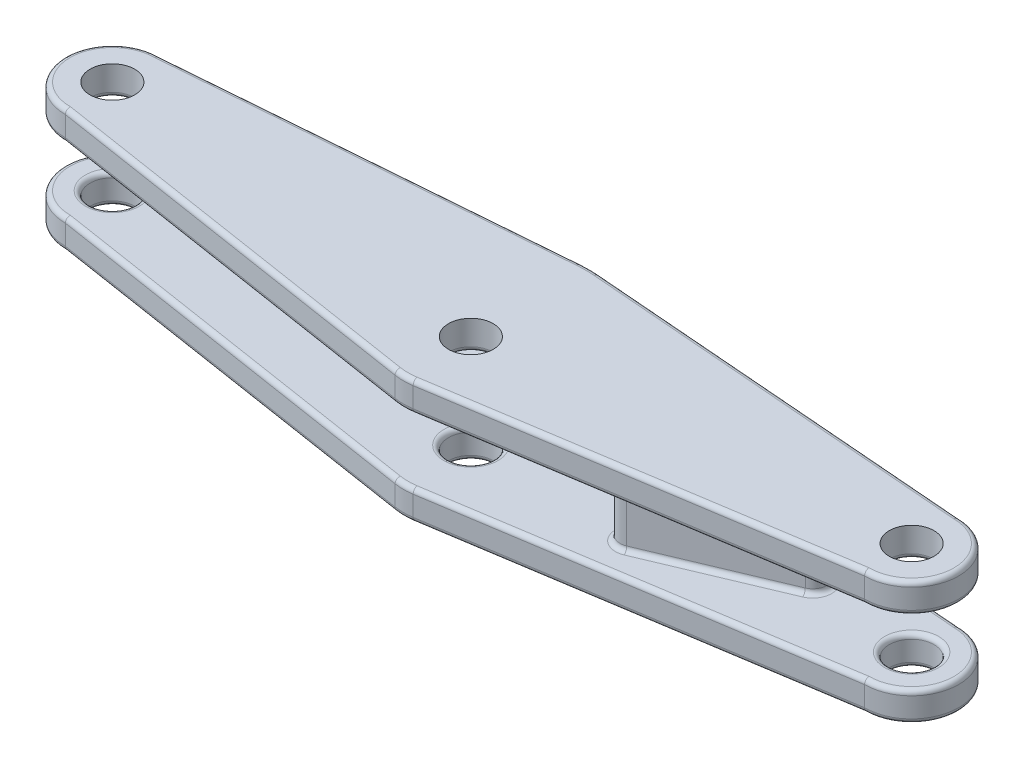
SolidWorks part; units mm, degrees
ref_plane "Front Plane" through (0, 0, 0) normal (0, 0, 1) x (1, 0, 0)
ref_plane "Top Plane" through (0, 0, 0) normal (0, 1, 0) x (1, 0, 0)
ref_plane "Right Plane" through (0, 0, 0) normal (1, 0, 0) x (0, 0, -1)
sketch "Sketch1" plane through (0, 0, 0) normal (0, 1, 0) x (1, 0, 0)
  line L0 (0, -12.9135) -> (0, 12.9135) construction
  line L1 (-15.3027, 0) -> (15.3027, 0) construction
  line L2 (-17, 2) -> (-0.3958, 3.3186)
  line L3 (0.3958, 3.3186) -> (17, 2)
  line L4 (-17, -2) -> (-0.3851, -4.59)
  line L5 (0.3851, -4.59) -> (17, -2)
  circle A0 centre (-17, 0) radius 0.95
  circle A1 centre (17, 0) radius 0.95
  arc A2 (-17, 2) -> (-17, -2) centre (-17, 0) ccw
  arc A3 (17, 2) -> (17, -2) centre (17, 0) cw
  arc A4 (-0.3958, 3.3186) -> (0.3958, 3.3186) centre (0, -1.6657) cw
  arc A5 (-0.3851, -4.59) -> (0.3851, -4.59) centre (0, -2.1198) ccw
  circle A6 centre (0, -1.75) radius 0.95
  point P8 (0, 0)
  point P11 (0, 0)
  point P17 (0, 3.35)
  point P23 (0, -4.65)
  dimension "D1" = 1.9
  dimension "D2" = 1.9
  dimension "D4" = 4
  dimension "D7" = 5
  dimension "D8" = 2.5
  dimension "D10" = 1.9
  dimension "D3" = 34
  dimension "D5" = 2
  dimension "D6" = 8
  dimension "D9" = 3.35
  dimension "D11" = 1.75
extrude "Boss-Extrude1" add sketch "Sketch1" along normal mid plane 5.25
sketch "Sketch2" plane through (0, 0, 0) normal (0, 0, 1) x (1, 0, 0)
  line L0 (-17, 2.625) -> (-0.3851, 2.625) construction
  line L1 (-19, 1.375) -> (19, 1.375)
  line L2 (-19, 1.375) -> (-19, -1.375)
  line L3 (-19, -1.375) -> (19, -1.375)
  line L4 (19, 1.375) -> (19, -1.375)
  line L5 (-19, 1.375) -> (19, -1.375) construction
  line L6 (-19, -1.375) -> (19, 1.375) construction
  line L7 (-19, 2.625) -> (-19, -2.625) construction
  point P0 (0, 0)
  dimension "D1" = 1.25
extrude "Cut-Extrude1" cut sketch "Sketch2" against normal mid plane 15.25
sketch "Sketch3" plane through (0, 2.625, 0) normal (0, 1, 0) x (1, 0, 0)
  line L0 (7, -1.8) -> (12.3458, 0.45) construction
  line L1 (6.7672, -1.247) -> (12.113, 1.003)
  line L2 (7.2328, -2.353) -> (12.5786, -0.103)
  line L3 (0, 0) -> (14.4976, 0) construction
  line L4 (12.3458, 0.45) -> (0.5962, 0.45) construction
  arc A0 (6.7672, -1.247) -> (7.2328, -2.353) centre (7, -1.8) ccw
  arc A1 (12.5786, -0.103) -> (12.113, 1.003) centre (12.3458, 0.45) ccw
  point P2 (9.6729, -0.675)
  dimension "D2" = 0.6
  dimension "D1" = 5.8
  dimension "D3" = 7
  dimension "D4" = 0.45
  dimension "D5" = 2.25
extrude "Boss-Extrude2" add sketch "Sketch3" against normal through all
fillet "Fillet1" radius 0.2 49 edges at (-8.6925, 1.375, 3.295) (0, 1.375, 4.6198) (8.6925, 1.375, 3.295) (19, 1.375, 0) (8.6979, 1.375, -2.6593) (0, 1.375, -3.3343) (-8.6979, 1.375, -2.6593) (-19, 1.375, 0) (17, 1.375, 0.95) (-17, 1.375, 0.95) (9.4401, 1.375, 0.122) (12.8988, 1.375, -0.6828) (9.9057, 1.375, 1.228) (6.447, 1.375, 2.0328) (-8.6979, -1.375, -2.6593) (0, -1.375, -3.3343) (8.6979, -1.375, -2.6593) (19, -1.375, 0) (8.6925, -1.375, 3.295) (0, -1.375, 4.6198) (-8.6925, -1.375, 3.295) (-19, -1.375, 0) (17, -1.375, -0.95) (-17, -1.375, -0.95) (12.8988, -1.375, -0.6828) (9.4401, -1.375, 0.122) (6.447, -1.375, 2.0328) (9.9057, -1.375, 1.228) (17, -2.625, 0.95) (-17, -2.625, 0.95) (-8.6925, -2.625, 3.295) (0, -2.625, 4.6198) (8.6925, -2.625, 3.295) (19, -2.625, 0) (8.6979, -2.625, -2.6593) (0, -2.625, -3.3343) (-8.6979, -2.625, -2.6593) (-19, -2.625, 0) (-8.6979, 2.625, -2.6593) (0, 2.625, -3.3343) (8.6979, 2.625, -2.6593) (19, 2.625, 0) (8.6925, 2.625, 3.295) (0, 2.625, 4.6198) (-8.6925, 2.625, 3.295) (-19, 2.625, 0) (0, 1.375, 2.7) (0, -1.375, 0.8) (0, -2.625, 2.7)
